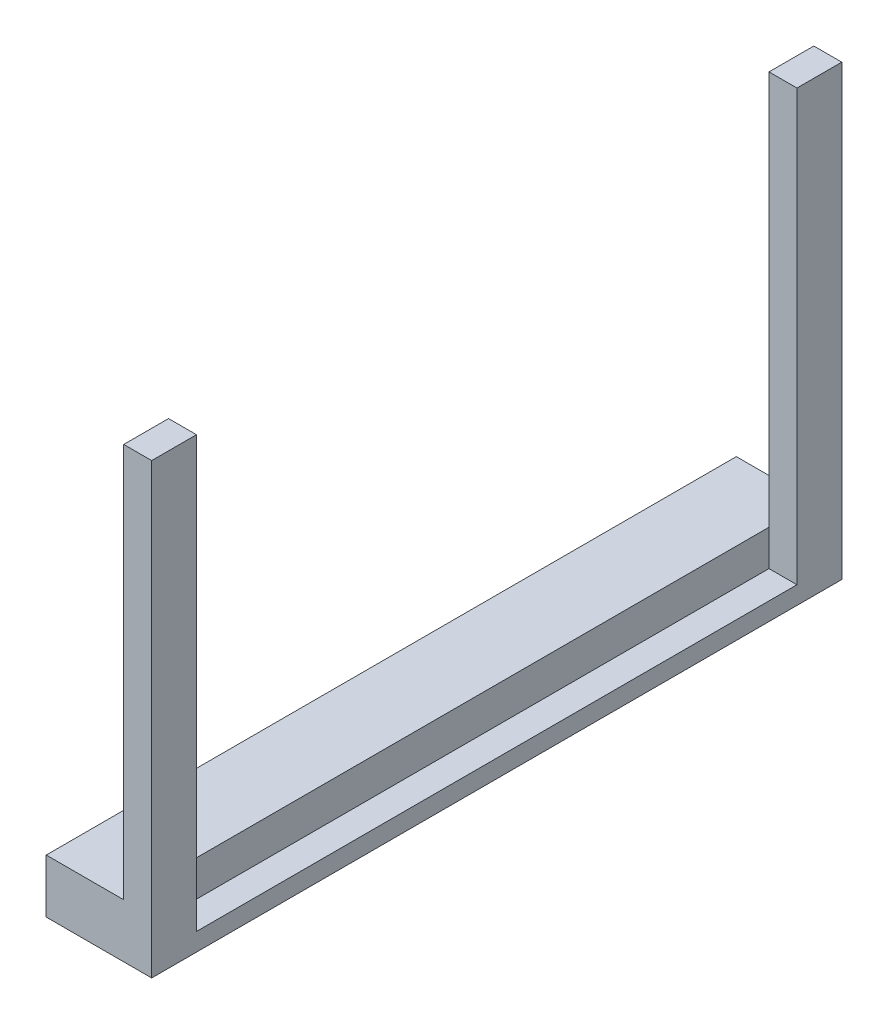
SolidWorks part; units mm, degrees
ref_plane "Front Plane" through (0, 0, 0) normal (0, 0, 1) x (1, 0, 0)
ref_plane "Top Plane" through (0, 0, 0) normal (0, 1, 0) x (1, 0, 0)
ref_plane "Right Plane" through (0, 0, 0) normal (1, 0, 0) x (0, 0, -1)
sketch "Sketch1" plane through (0, 0, 0) normal (0, 0, 1) x (1, 0, 0)
  line L1 (-1.56, 24) -> (1.56, 24)
  line L2 (-1.56, 24) -> (-1.56, -24)
  line L3 (-1.56, -24) -> (1.56, -24)
  line L4 (1.56, 24) -> (1.56, -24)
  line L5 (-1.56, 24) -> (1.56, -24) construction
  line L6 (-1.56, -24) -> (1.56, 24) construction
  point P0 (0, 0)
  dimension "D1" = 3.12
  dimension "D2" = 48
extrude "Boss-Extrude1" add sketch "Sketch1" against normal blind 5
ref_plane "Plane3" through (0, -24, 0) normal (0, -1, 0) x (-1, 0, 0)
sketch "Sketch3" plane through (0, -24, 0) normal (0, -1, 0) x (-1, 0, 0)
  line L0 (2.345, 0) -> (4.1256, 0)
  line L1 (-1.56, 0) -> (2.345, 0)
  line L2 (-1.56, 0) -> (-1.56, 5)
  line L3 (-1.56, 5) -> (1.56, 5)
  line L5 (4.1256, 0) -> (4.1256, 5)
  line L6 (4.1256, 5) -> (1.56, 5)
extrude "Boss-Extrude2" add sketch "Sketch3" along normal blind 2
ref_plane "Plane4" through (0, 0, -5) normal (0, 0, -1) x (-1, 0, 0)
sketch "Sketch4" plane through (0, 0, -5) normal (0, 0, -1) x (-1, 0, 0)
  line L1 (-1.56, -26) -> (4.1256, -26)
  line L2 (-1.56, -26) -> (-1.56, -24)
  line L3 (-1.56, -24) -> (4.1256, -24)
  line L4 (4.1256, -26) -> (4.1256, -24)
extrude "Boss-Extrude3" add sketch "Sketch4" along normal blind 33.5
mirror "Mirror7" about plane through (0, 0, -38.5) normal (0, 0, 1) of bodies 103
ref_plane "Plane5" through (-4.1256, 0, 0) normal (-1, 0, 0) x (0, 0, 1)
sketch "Sketch5" plane through (-4.1256, 0, 0) normal (-1, 0, 0) x (0, 0, 1)
  line L1 (0, -26) -> (-77, -26)
  line L2 (0, -26) -> (0, -24)
  line L3 (0, -24) -> (-77, -24)
  line L4 (-77, -26) -> (-77, -24)
extrude "Boss-Extrude4" add sketch "Sketch5" along normal blind 6.08
ref_plane "Plane6" through (0, -24, 0) normal (0, 1, 0) x (1, 0, 0)
sketch "Sketch6" plane through (0, -24, 0) normal (0, 1, 0) x (1, 0, 0)
  line L1 (-1.56, 0) -> (-10.2056, 0)
  line L2 (-1.56, 0) -> (-1.56, 77)
  line L3 (-1.56, 77) -> (-10.2056, 77)
  line L4 (-10.2056, 0) -> (-10.2056, 77)
extrude "Boss-Extrude5" add sketch "Sketch6" along normal blind 4
